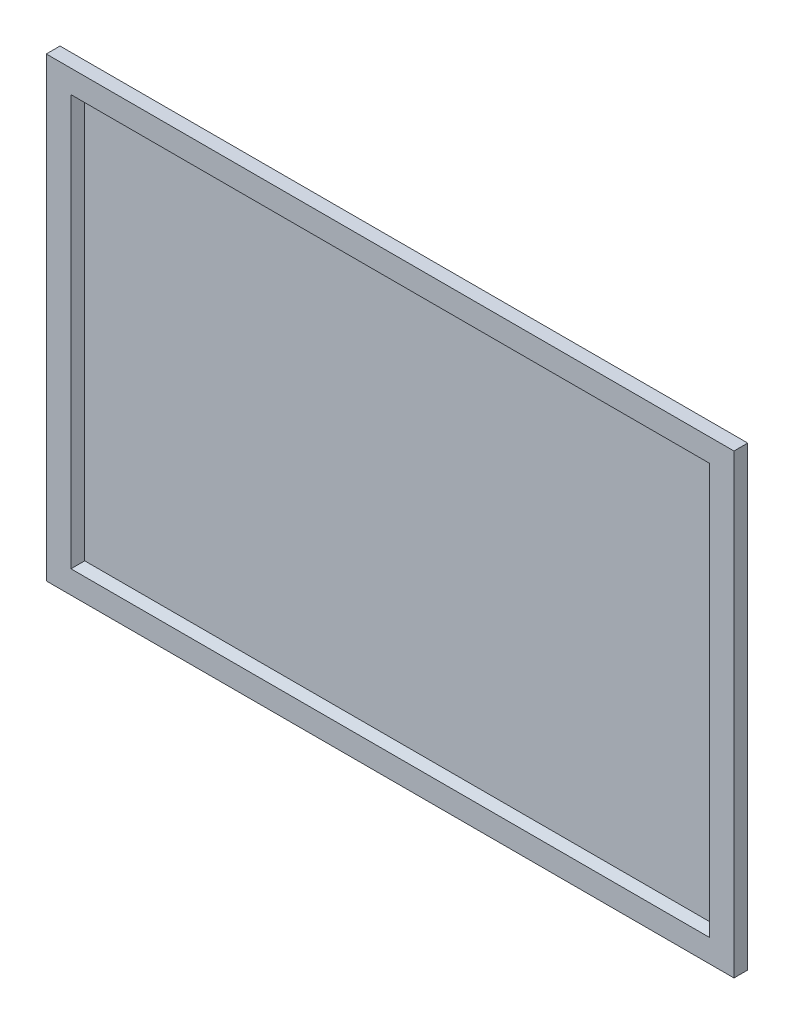
SolidWorks part; units mm, degrees
ref_plane "Front Plane" through (0, 0, 0) normal (0, 0, 1) x (1, 0, 0)
ref_plane "Top Plane" through (0, 0, 0) normal (0, 1, 0) x (1, 0, 0)
ref_plane "Right Plane" through (0, 0, 0) normal (1, 0, 0) x (0, 0, -1)
sketch "Sketch2" plane through (0, 0, 0) normal (0, 0, 1) x (1, 0, 0)
  line L1 (-500, -331.8182) -> (500, -331.8182)
  line L2 (-500, -331.8182) -> (-500, 331.8182)
  line L3 (-500, 331.8182) -> (500, 331.8182)
  line L4 (500, -331.8182) -> (500, 331.8182)
  line L5 (-500, -331.8182) -> (500, 331.8182) construction
  line L6 (-500, 331.8182) -> (500, -331.8182) construction
  point P0 (0, 0)
  dimension "D1" = 1000
extrude "Boss-Extrude1" add sketch "Sketch2" along normal blind 20
sketch "Sketch3" plane through (0, 0, 20) normal (0, 0, 1) x (1, 0, 0)
  line L1 (-474.0761, -308.5617) -> (474.0761, -308.5617)
  line L2 (-474.0761, -308.5617) -> (-474.0761, 308.5617)
  line L3 (-474.0761, 308.5617) -> (474.0761, 308.5617)
  line L4 (474.0761, -308.5617) -> (474.0761, 308.5617)
  line L5 (-474.0761, -308.5617) -> (474.0761, 308.5617) construction
  line L6 (-474.0761, 308.5617) -> (474.0761, -308.5617) construction
  point P0 (0, 0)
extrude "Cut-Extrude1" cut sketch "Sketch3" against normal blind 10
chamfer "Chamfer1" distance 20 angle 45 4 edges at (0, -308.5617, 10) (-474.0761, 0, 10) (0, 308.5617, 10) (474.0761, 0, 10)
